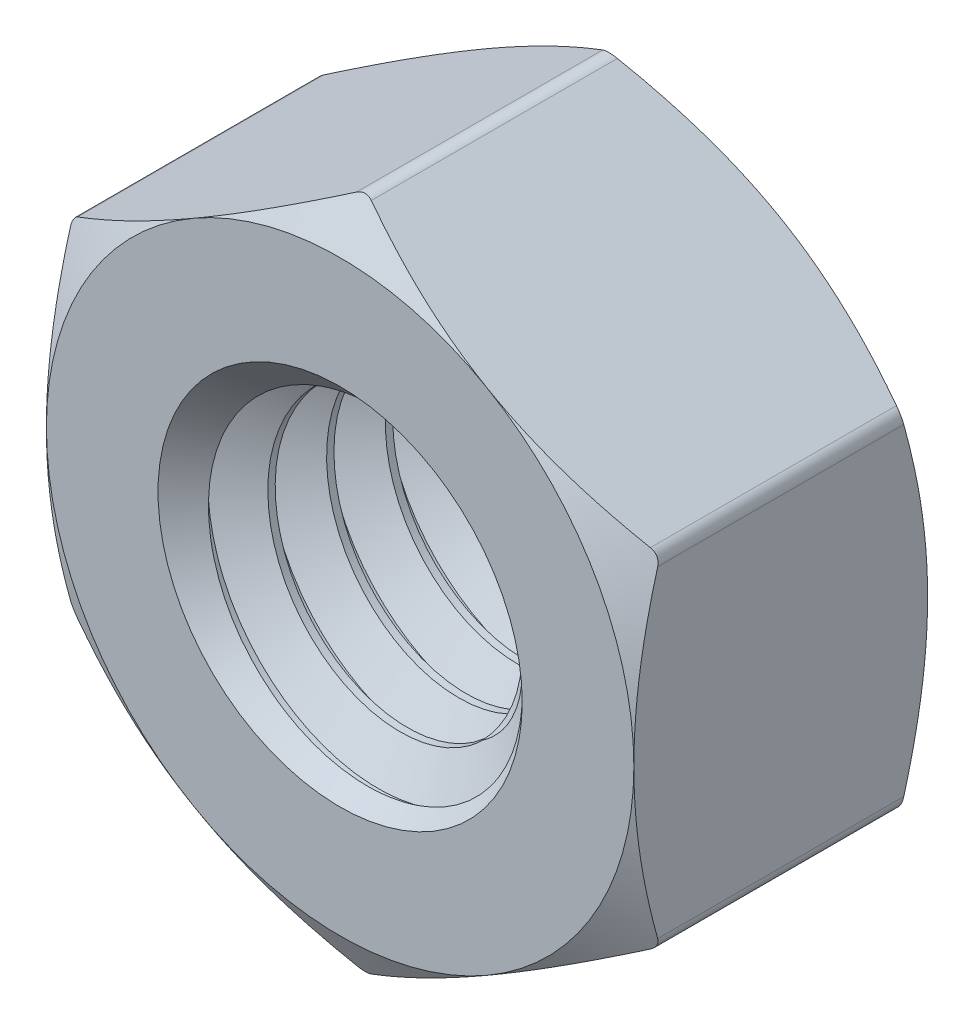
SolidWorks part; units mm, degrees
ref_plane "Front" through (0, 0, 0) normal (0, 0, 1) x (1, 0, 0)
ref_plane "Top" through (0, 0, 0) normal (0, 1, 0) x (1, 0, 0)
ref_plane "Right" through (0, 0, 0) normal (1, 0, 0) x (0, 0, -1)
sketch "Sketch1" plane through (0, 0, 0) normal (0, 0, 1) x (1, 0, 0)
  line L0 (0, 3) -> (0, 2) construction
  line L1 (-5, 2.8868) -> (-5, -2.8868)
  line L2 (-5, -2.8868) -> (0, -5.7735)
  line L3 (0, -5.7735) -> (5, -2.8868)
  line L4 (5, -2.8868) -> (5, 2.8868)
  line L5 (5, 2.8868) -> (0, 5.7735)
  line L6 (0, 5.7735) -> (-5, 2.8868)
  circle A0 centre (0, 0) radius 5 construction
  circle A1 centre (0, 0) radius 3 construction
  point P10 (0, 3)
  dimension "Width" = 10
  dimension "Thread Size" = 6
  dimension "Thread Pitch" = 1
sketch "Sketch2" plane through (0, 0, 0) normal (1, 0, 0) x (0, 0, -1)
  line L0 (-2.5, 0) -> (2.5, 0) construction
  line L1 (-2.5, 5.7735) -> (2.5, 5.7735) construction
  dimension "Height" = 5
sketch "Sketch15" plane through (0, 0, 0) normal (0, 0, 1) x (1, 0, 0)
  line L1 (0, 5.7735) -> (-5, 2.8868)
  line L2 (-5, 2.8868) -> (-5, -2.8868)
  line L3 (-5, -2.8868) -> (0, -5.7735)
  line L4 (0, -5.7735) -> (5, -2.8868)
  line L5 (5, -2.8868) -> (5, 2.8868)
  line L6 (5, 2.8868) -> (0, 5.7735)
  circle A0 centre (0, 0) radius 5 construction
extrude "Boss-Extrude2" add sketch "Sketch15" along normal mid plane 5
sketch "Sketch16" plane through (0, 0, 0) normal (0, 0, 1) x (1, 0, 0)
  circle A0 centre (0, 0) radius 3 construction
  circle A1 centre (0, 0) radius 3
sketch "Sketch4" plane through (0, 0, -2.5) normal (0, 0, -1) x (-1, 0, 0)
  circle A0 centre (0, 0) radius 3 construction
  circle A1 centre (0, 0) radius 3
extrude "Cut-Extrude4" cut sketch "Sketch16" against normal through all both and the other way through all
sketch "Sketch7" plane through (0, 0, 2.5) normal (0, 0, 1) x (1, 0, 0)
  circle A0 centre (0, 0) radius 5 construction
  circle A1 centre (0, 0) radius 5
extrude "Cut-Extrude5" cut sketch "Sketch7" against normal through all draft 60 flip side to cut
mirror "Mirror4" about plane through (0, 0, 0) normal (0, 0, 1) of "Cut-Extrude5"
fillet "Fillet2" radius 0.25 6 edges at (-5, 2.8868, 0) (-5, -2.8868, 0) (0, -5.7735, 0) (5, -2.8868, 0) (5, 2.8868, 0) (0, 5.7735, 0)
sketch "Sketch8" plane through (0, 0, 2.5) normal (0, 0, 1) x (1, 0, 0)
  line L0 (0.7765, -2.8978) -> (0, 0) construction
  line L2 (0, 3) -> (0, 2) construction
  circle A0 centre (0, 0) radius 3 construction
  point P0 (0.7765, -2.8978)
  dimension "D1" = 15
sketch "Sketch13" plane through (0, 0, -2.5) normal (0, 0, -1) x (-1, 0, 0)
  circle A0 centre (0, 0) radius 3 construction
  circle A1 centre (0, 0) radius 3
extrude "Boss-Extrude1" add sketch "Sketch13" against normal up to surface (5 mm away) separate body up to face at (3, 0, 2.5)
curve "Helix/Spiral3" pitch 1 height 7 radius 3 centre (0, 0, -2.5) axis (0, 0, 1) start towards (0, 1, 0)
sketch "Sketch12" plane through (0, 0, 0) normal (1, 0, 0) x (0, 0, -1)
  line L0 (3.375, 3) -> (2.5, 3)
  line L1 (3.375, 3) -> (3, 2.3505)
  line L2 (3, 2.3505) -> (2.875, 2.3505)
  line L3 (2.875, 2.3505) -> (2.5, 3)
  line L4 (2.9375, 2.3505) -> (2.9375, 3) construction
  line L5 (2.6875, 2.6752) -> (3.1875, 2.6752) construction
  dimension "D1" = 60
  dimension "D2" = 0.125
  dimension "D3" = 0.5
sweep "Cut-Sweep1" cut profiles "Sketch12" path "Helix/Spiral3" align with end faces yes
sketch "Sketch17" plane through (0, 0, 2.5) normal (0, 0, 1) x (1, 0, 0)
  circle A1 centre (0, 0) radius 3
  circle A2 centre (0, 0) radius 3
  dimension "D1" = 0
extrude "Boss-Extrude3" add sketch "Sketch17" against normal up to surface (5 mm away) up to face at (3, 0, -2.5)
combine bodies "Combine1" operation type subtract main body 127 bodies to subtract 118
sketch "Sketch10" plane through (0, 0, 2.5) normal (0, 0, 1) x (1, 0, 0)
  circle A0 centre (0, 0) radius 3 construction
  circle A1 centre (0, 0) radius 3 construction
  circle A2 centre (0, 0) radius 3.1
extrude "Cut-Extrude2" cut sketch "Sketch10" against normal through all draft 45
sketch "Sketch11" plane through (0, 0, -2.5) normal (0, 0, -1) x (-1, 0, 0)
  circle A1 centre (0, 0) radius 3.1 construction
  circle A2 centre (0, 0) radius 3.1
extrude "Cut-Extrude3" cut sketch "Sketch11" against normal through all draft 45
equation "\"D1\"= \"Height@Sketch2\""
equation "\"D3@Helix/Spiral3\"=\"Height@Sketch2\"+\"Thread Pitch@Sketch1\"*2"
equation "\"D4@Helix/Spiral3\"=\"Thread Pitch@Sketch1\""
equation "\"D2@Sketch12\" = \"D4@Helix/Spiral3\"*.125"
equation "\"D3@Sketch12\" = \"D4@Helix/Spiral3\"*.50"
equation "\"D1@Boss-Extrude2\"=\"Height@Sketch2\""
equation "\"D1@Fillet2\"=\"Width@Sketch1\"*0.025"
equation "\"D1@Sketch10\"=\"Thread Pitch@Sketch1\"*0.1"
